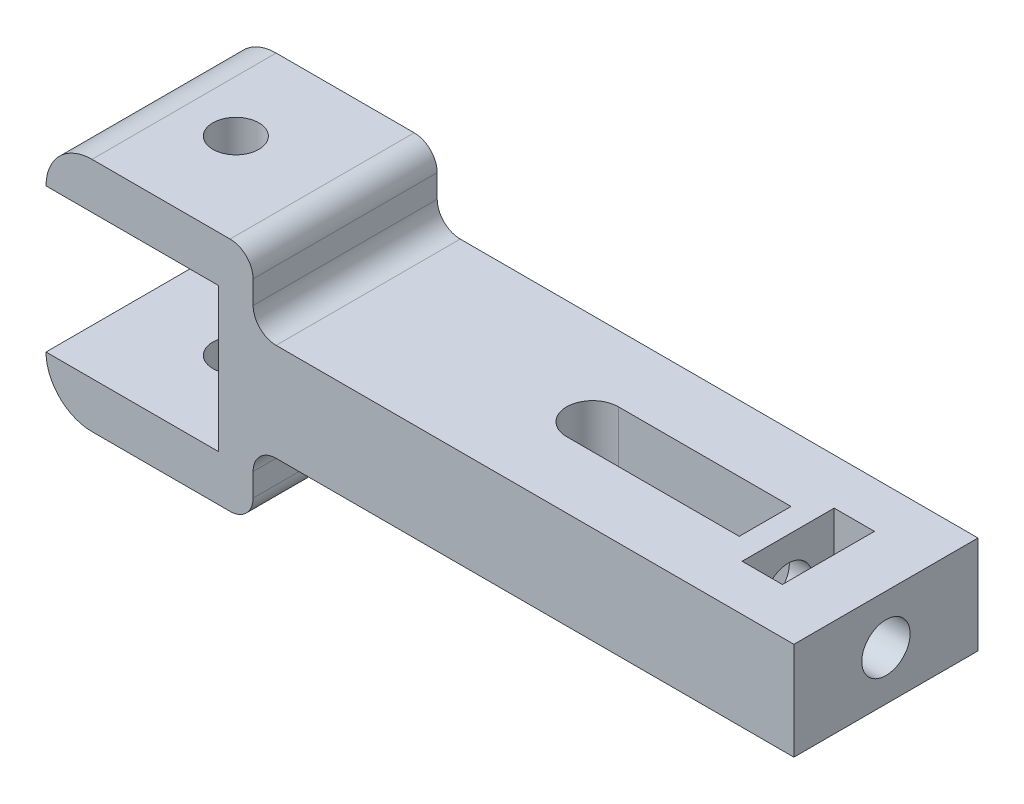
SolidWorks part; units mm, degrees
ref_plane "Front Plane" through (0, 0, 0) normal (0, 0, 1) x (1, 0, 0)
ref_plane "Top Plane" through (0, 0, 0) normal (0, 1, 0) x (1, 0, 0)
ref_plane "Right Plane" through (0, 0, 0) normal (1, 0, 0) x (0, 0, -1)
sketch "Sketch1" plane through (0, 0, 0) normal (0, 0, 1) x (1, 0, 0)
  line L0 (0, 0) -> (-47, 0)
  line L1 (-47, 0) -> (-47, 6)
  line L2 (-47, 6) -> (-65, 6)
  line L3 (-65, 6) -> (-65, 2)
  line L4 (-65, 2) -> (-50, 2)
  line L5 (-50, 2) -> (-50, -10.5)
  line L6 (0, 0) -> (0, -8.5)
  line L7 (0, -4.25) -> (-50, -4.25) construction
  line L8 (-65, -10.5) -> (-50, -10.5)
  line L9 (-65, -14.5) -> (-65, -10.5)
  line L10 (-47, -14.5) -> (-65, -14.5)
  line L11 (-47, -8.5) -> (-47, -14.5)
  line L12 (0, -8.5) -> (-47, -8.5)
  dimension "D1" = 65
  dimension "D2" = 15
  dimension "D3" = 4.25
  dimension "D4" = 6.25
  dimension "D5" = 4
  dimension "D6" = 18
extrude "Boss-Extrude1" add sketch "Sketch1" along normal blind 16
sketch "Sketch2" plane through (0, 0, 0) normal (0, 1, 0) x (1, 0, 0)
  line L0 (0, -8) -> (-47, -8) construction
  line L1 (0, -16) -> (0, 0) construction
  line L2 (-47, -16) -> (-47, 0) construction
  line L4 (-8.5, -4) -> (-5, -4)
  line L5 (-8.5, -4) -> (-8.5, -12)
  line L6 (-8.5, -12) -> (-5, -12)
  line L7 (-5, -4) -> (-5, -12)
  line L8 (-8.5, -4) -> (-5, -12) construction
  line L9 (-8.5, -12) -> (-5, -4) construction
  line L10 (-25.5, -10.25) -> (-10.5, -10.25)
  line L12 (-25.5, -5.75) -> (-10.5, -5.75)
  line L13 (-10.5, -10.25) -> (-10.5, -5.75)
  line L14 (-25.5, -10.25) -> (-10.5, -5.75) construction
  line L15 (-25.5, -5.75) -> (-10.5, -10.25) construction
  arc A0 (-25.5, -5.75) -> (-25.5, -10.25) centre (-25.5, -8) ccw
  point P6 (-6.75, -8)
  point P11 (-18, -8)
  dimension "D7" = 2.25
  dimension "D1" = 8
  dimension "D2" = 3.5
  dimension "D3" = 5
  dimension "D4" = 2
  dimension "D5" = 4.5
  dimension "D6" = 15
extrude "Cut-Extrude1" cut sketch "Sketch2" against normal through all
sketch "Sketch3" plane through (0, 0, 0) normal (1, 0, 0) x (0, 0, -1)
  line L0 (-8, 0) -> (-8, -8.5) construction
  line L1 (-16, 0) -> (0, 0) construction
  line L2 (-16, -8.5) -> (0, -8.5) construction
  circle A0 centre (-8, -4.25) radius 2.1
  dimension "D1" = 4.2
extrude "Cut-Extrude2" cut sketch "Sketch3" against normal up to surface (10.5 mm away) up to face at (-10.5, -4.25, 8)
fillet "Fillet1" radius 2 4 edges at (-47, -8.5, 8) (-47, 6, 8) (-47, 0, 8) (-47, -14.5, 8)
sketch "Sketch4" plane through (0, -10.5, 0) normal (0, 1, 0) x (1, 0, 0)
  line L0 (-65, -8) -> (-49, -8) construction
  line L1 (-65, -16) -> (-65, 0) construction
  line L2 (-49, 0) -> (-49, -16) construction
  circle A0 centre (-57, -8) radius 9
  dimension "D1" = 18
extrude "Cut-Extrude3" cut sketch "Sketch4" along normal up to surface (12.5 mm away) up to face at (-57.5, 2, 8)
sketch "Sketch5" plane through (0, 6, 0) normal (0, 1, 0) x (1, 0, 0)
  line L0 (-65, -8) -> (-49, -8) construction
  line L1 (-65, -16) -> (-65, 0) construction
  line L2 (-49, -16) -> (-49, 0) construction
  circle A0 centre (-56.5, -8) radius 2
  dimension "D1" = 4
  dimension "D2" = 8.5
extrude "Cut-Extrude4" cut sketch "Sketch5" against normal through all
fillet "Fillet2" radius 4 2 edges at (-65, -14.5, 8) (-65, 6, 8)
equation "\"X-ROD-SPACING\"=45"
equation "\"Y-ROD-SPACING\"=75"
equation "\"Z-ROD-SPACING\"=17.5"
equation "\"Y-BED-OFFSET\"=2"
equation "\"Y-BED-ROD-INSET\"=3.5"
equation "\"T-SLOT-NUT-FILLET-RADIUS\"=0.5"
equation "\"T-SLOT-SCREW-SHAFT-RADIUS\"=1.55"
equation "\"T-SLOT-SCREW-SHAFT-CUTOUT-LENGTH\"=11"
equation "\"T-SLOT-NUT-DEPTH\"=3.5"
equation "\"T-SLOT-NUT-WIDTH\"=2.85"
equation "\"T-SLOT-NUT-END-DISTANCE\"=8"
equation "\"ACRYLIC-THICKNESS\"=10"
equation "\"ACRYLIC-TAB-CUTOUT-SIZE\"=\"ACRYLIC-THICKNESS\"+\"ACRYLIC-TAB-TOLERANCE\"*2"
equation "\"ACRYLIC-TAB-WIDTH\"=\"ACRYLIC-THICKNESS\""
equation "\"ACRYLIC-M3-HOLE\"=2.9"
equation "\"SMOOTHROD-CAP-SCREW-DISTANCE\"=20"
equation "\"FRAME-WIDTH-INNER\"=370"
equation "\"NEMA17-HOLE-SPACING\"=31"
equation "\"NEMA17-CENTRAL-CUTOUT\"=22.5"
equation "\"Z-BRACKET-REACH\"=55"
equation "\"TOP-BRACKET-SPACING\"=40"
equation "\"SMOOTHROD-X-LENGTH\"=350"
equation "\"SMOOTHROD-Y-LENGTH\"=350"
equation "\"SMOOTHROD-Z-LENGTH\"=350"
equation "\"SMOOTHROD-TIGHTENING-HEADROOM\"=.25"
equation "\"LEADSCREW-Z-LENGTH\"=300"
equation "\"SCREW-HEAD-RADIUS\"=6"
equation "\"PRINTED-X-SMOOTHROD-DIAMETER\"=8.8"
equation "\"PRINTED-X-SMOOTHROD-CUTOUT\"=10"
equation "\"PRINTED-X-BASE-HEIGHT\"=10"
equation "\"PRINTED-LM8UU-CUTOUT-SIZE\"=15.5"
equation "\"PRINTED-LM8UU-CUTOUT-LENGTH\"=24.5"
equation "\"PRINTED-X-IDLER-HEIGHT\"=16"
equation "\"D1@Boss-Extrude1\"=\"PRINTED-X-IDLER-HEIGHT\""
